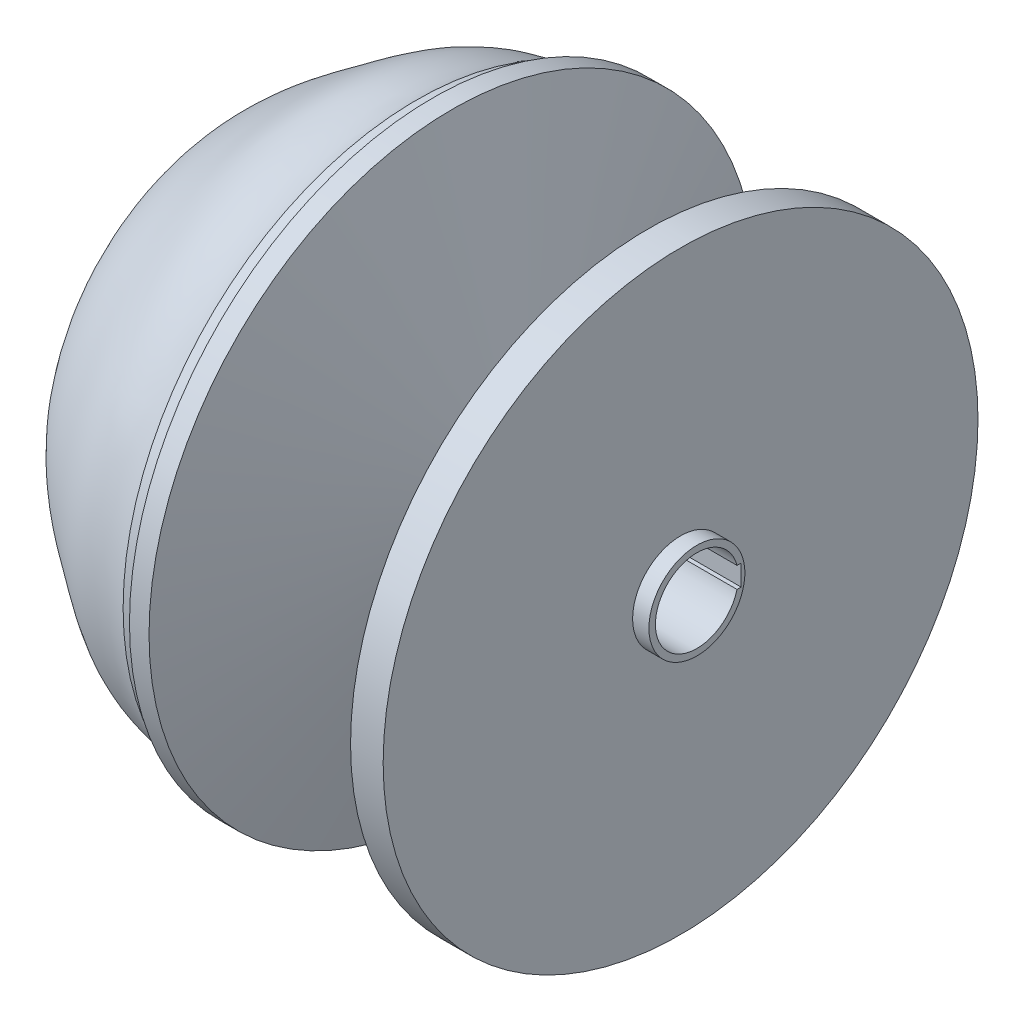
SolidWorks part; units mm, degrees
ref_plane "Front Plane" through (0, 0, 0) normal (0, 0, 1) x (1, 0, 0)
ref_plane "Top Plane" through (0, 0, 0) normal (0, 1, 0) x (1, 0, 0)
ref_plane "Right Plane" through (0, 0, 0) normal (1, 0, 0) x (0, 0, -1)
sketch "Sketch1" plane through (0, 0, 0) normal (0, 0, 1) x (1, 0, 0)
  line L0 (-81.8357, 0) -> (85.1506, 0) construction
  line L1 (-80.912, 0) -> (-80.912, 12.718)
  line L2 (-80.912, 12.718) -> (-70.912, 12.718)
  line L3 (-70.912, 12.718) -> (-70.912, 32.718)
  line L4 (-6.6076, 90) -> (-1.665, 90)
  line L5 (-1.665, 90) -> (-1.665, 93)
  line L6 (-1.665, 93) -> (4.335, 93)
  line L7 (4.335, 93) -> (23.8279, 15)
  line L8 (23.8279, 15) -> (48.8279, 15)
  line L9 (48.8279, 15) -> (64.335, 91.2022)
  line L10 (64.335, 91.2022) -> (74.335, 91.2022)
  line L11 (74.335, 91.2022) -> (74.335, 14.7093)
  line L12 (74.335, 14.7093) -> (79.335, 14.7093)
  line L13 (79.335, 14.7093) -> (79.335, 0)
  line L14 (-80.912, 0) -> (79.335, 0)
  spline S0 degree 3 poles (-70.912, 32.718) (-72.2965, 50.1852) (-58.6812, 63.1703) (-38.6366, 76.8934) (-26.2583, 86.8313) (-12.1521, 86.8994) (-6.6076, 90) knots 0 0 0 0 0.504233 0.563304 0.796603 1 1 1 1
  point P11 (0, 0)
  dimension "D1" = 10
  dimension "D2" = 15
  dimension "D3" = 93
  dimension "D4" = 160.247
  dimension "D5" = 10
  dimension "D6" = 5
  dimension "D7" = 6
  dimension "D8" = 3
  dimension "D9" = 60
  dimension "D10" = 25
revolve "Revolve1" add sketch "Sketch1" angle 360 about L0
sketch "Sketch2" plane through (79.335, 0, 0) normal (1, 0, 0) x (0, 0, -1)
  circle A0 centre (0, 0) radius 12.718
  dimension "D1" = 25.436
extrude "Cut-Extrude1" cut sketch "Sketch2" against normal blind 82.74
sketch "Sketch3" plane through (-80.912, 0, 0) normal (-1, 0, 0) x (0, 0, 1)
  circle A0 centre (0, 0) radius 10
  dimension "D1" = 20
extrude "Cut-Extrude2" cut sketch "Sketch3" against normal blind 79.507
chamfer "Chamfer1" distance 3 angle 30 1 edges at (-3.405, 0, -10) first distance on face at (-3.405, 0, -10)
sketch "Sketch4" plane through (79.335, 0, 0) normal (1, 0, 0) x (0, 0, -1)
  line L1 (11.8725, 3.1875) -> (13.5635, 3.1875)
  line L2 (11.8725, 3.1875) -> (11.8725, -3.1875)
  line L3 (11.8725, -3.1875) -> (13.5635, -3.1875)
  line L4 (13.5635, 3.1875) -> (13.5635, -3.1875)
  line L5 (11.8725, 3.1875) -> (13.5635, -3.1875) construction
  line L6 (11.8725, -3.1875) -> (13.5635, 3.1875) construction
  circle A0 centre (0, 0) radius 12.718 construction
  circle A1 centre (0, 0) radius 12.718 construction
  point P0 (12.718, 0)
  dimension "D1" = 6.375
  dimension "D2" = 0.8455
extrude "Cut-Extrude3" cut sketch "Sketch4" against normal blind 56
